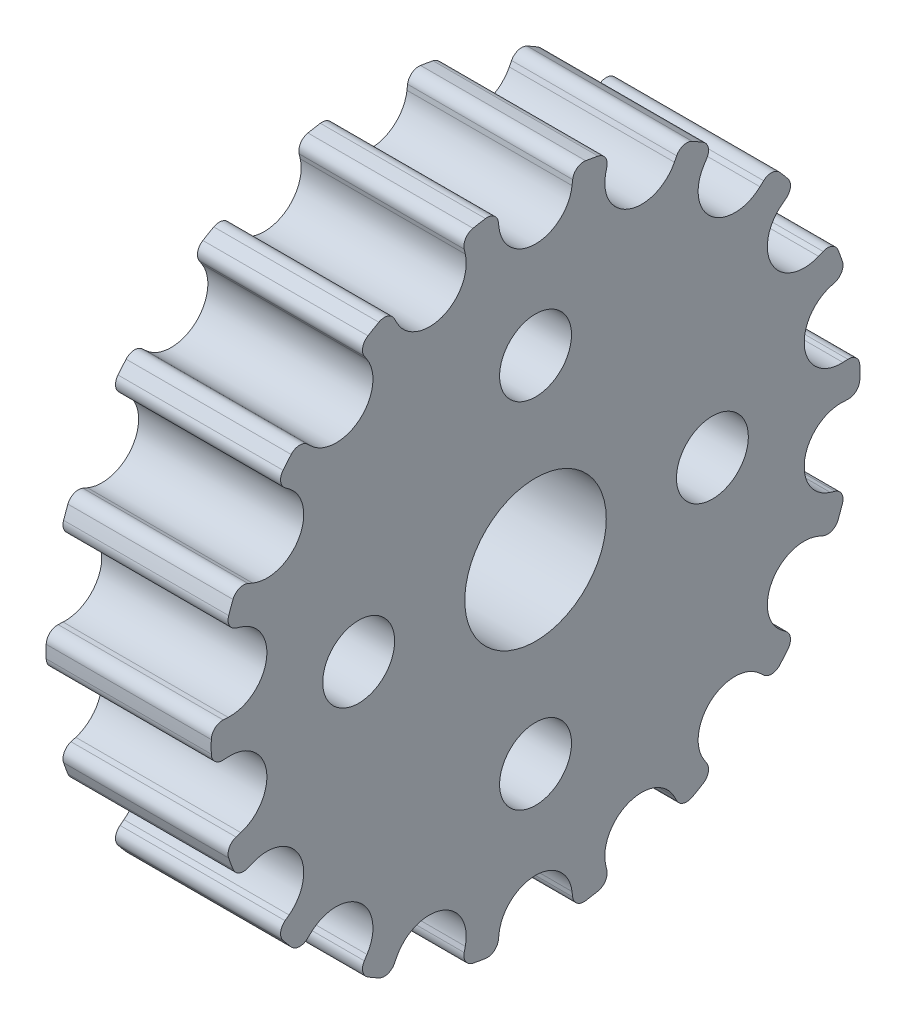
SolidWorks part; units mm, degrees
ref_plane "前视基准面" through (0, 0, 0) normal (0, 0, 1) x (1, 0, 0)
ref_plane "上视基准面" through (0, 0, 0) normal (0, 1, 0) x (1, 0, 0)
ref_plane "右视基准面" through (0, 0, 0) normal (1, 0, 0) x (0, 0, -1)
sketch "草图1" plane through (0, 0, 0) normal (0, 0, 1) x (1, 0, 0)
  line L0 (0, 0) -> (64.8368, 0) construction
  line L1 (0, 2.7506) -> (0, 13.753)
  line L2 (0, 13.753) -> (28, 13.753)
  line L3 (28, 13.753) -> (28, 5.5012)
  line L4 (28, 5.5012) -> (20, 5.5012)
  line L5 (20, 5.5012) -> (20, 2.7506)
  line L6 (20, 2.7506) -> (0, 2.7506)
  dimension "L" = 20
  dimension "B" = 28
  dimension "d" = 5.5012
  dimension "d1" = 11.0024
  dimension "da" = 27.506
revolve "旋转1" add sketch "草图1" angle 360 about L0
chamfer "倒角1" distance 1 angle 45 2 edges at (20, 0, 2.7506) (0, 0, 2.7506)
sketch "草图4" plane through (0, 0, 0) normal (-1, 0, 0) x (0, 0, 1)
  line L1 (-1, 2.5624) -> (1, 2.5624)
  line L2 (-1, 2.5624) -> (-1, 3.5624)
  line L3 (-1, 3.5624) -> (1, 3.5624)
  line L4 (1, 2.5624) -> (1, 3.5624)
  circle A0 centre (0, 0) radius 2.7506 construction
  dimension "键槽宽度" = 2
  dimension "t1" = 1
extrude "切除-拉伸1" cut sketch "草图4" against normal through all
ref_axis "基准轴1" through (-1.4, 0, 0) along (1, 0, 0)
sketch "草图6" plane through (0, 0, 0) normal (1, 0, 0) x (0, 0, -1)
  line L0 (0, 0) -> (0, 30.6512) construction
  line L1 (1.5741, 13.1722) -> (1.5484, 12.9629)
  line L2 (2.5975, 13.5055) -> (2.7942, 15.107)
  line L3 (-2.5975, 13.5055) -> (-2.7942, 15.107)
  line L4 (-1.5741, 13.1722) -> (-1.5484, 12.9629)
  circle A0 centre (0, 0) radius 13.753 construction
  circle A1 centre (0, 0) radius 11.593 construction
  arc A2 (-1.5484, 12.9629) -> (1.5484, 12.9629) centre (0, 13.153) ccw
  arc A3 (2.7942, 15.107) -> (-2.7942, 15.107) centre (0, 0) ccw
  arc A4 (1.5741, 13.1722) -> (2.1246, 13.5879) centre (2.0505, 13.1137) cw
  arc A5 (2.1246, 13.5879) -> (2.5975, 13.5055) centre (0, 0) cw
  arc A6 (-2.1246, 13.5879) -> (-2.5975, 13.5055) centre (0, 0) ccw
  arc A7 (-1.5741, 13.1722) -> (-2.1246, 13.5879) centre (-2.0505, 13.1137) ccw
  point P7 (0, 3.25)
  point P8 (0, 28.4912)
  point P15 (1.6334, 13.6557)
  dimension "D1" = 23.186
  dimension "ra" = 0.48
  dimension "rf" = 1.56
  dimension "hg" = 2.16
  dimension "D3" = 0.48
  dimension "D4" = 1.6136
  dimension "angle" = 14
  dimension "bw" = 3.25
extrude "切除-拉伸2" cut sketch "草图6" along normal up to next
pattern_circular "阵列(圆周)3" count 18 over 360 about axis through (-1.4, 0, 0) along (1, 0, 0) of "切除-拉伸2"
sketch "草图7" plane through (28, 0, 0) normal (1, 0, 0) x (0, 0, -1)
  circle A0 centre (0, 0) radius 25
  dimension "D1" = 50
extrude "切除-拉伸3" cut sketch "草图7" against normal offset from surface (21 mm away) 7 up to face at (0, 0, -3.7506)
sketch "草图8" plane through (7, 0, 0) normal (1, 0, 0) x (0, 0, -1)
  circle A0 centre (0, 0) radius 5
  dimension "D1" = 10
extrude "凸台-拉伸1" add sketch "草图8" against normal up to surface (7 mm away) up to face at (0, 0, -3.7506)
sketch "草图10" plane through (7, 0, 0) normal (1, 0, 0) x (0, 0, -1)
  circle A0 centre (0, 0) radius 3
  dimension "D1" = 6
extrude "切除-拉伸4" cut sketch "草图10" against normal blind 10
sketch "草图11" plane through (7, 0, 0) normal (1, 0, 0) x (0, 0, -1)
  circle A0 centre (0, 0) radius 7.5 construction
  circle A1 centre (0, 7.5) radius 1.525
  circle A2 centre (7.5, 0) radius 1.525
  circle A3 centre (0, -7.5) radius 1.525
  circle A4 centre (-7.5, 0) radius 1.525
  point P14 (0, 0)
  dimension "D1" = 15
  dimension "D2" = 3.05
  dimension "D3" = 4
extrude "切除-拉伸5" cut sketch "草图11" against normal blind 46
sketch "草图12" [suppressed] plane through (7, 0, 0) normal (1, 0, 0) x (0, 0, -1)
  circle A0 centre (0, 0) radius 8 construction
  circle A1 centre (0, 8) radius 1.5
  circle A2 centre (6.9282, 4) radius 1.5
  circle A3 centre (6.9282, -4) radius 1.5
  circle A4 centre (0, -8) radius 1.5
  circle A5 centre (-6.9282, -4) radius 1.5
  circle A6 centre (-6.9282, 4) radius 1.5
  point P14 (0, 0)
  dimension "D1" = 16
  dimension "D2" = 3
  dimension "D3" = 6
extrude "切除-拉伸6" [suppressed] cut sketch "草图12" against normal blind 32
equation "\"D1@草图6\" = \"da@草图1\"  - \"hg@草图6\" - \"hg@草图6\""
equation "\"D3@草图6\" = \"ra@草图6\""
